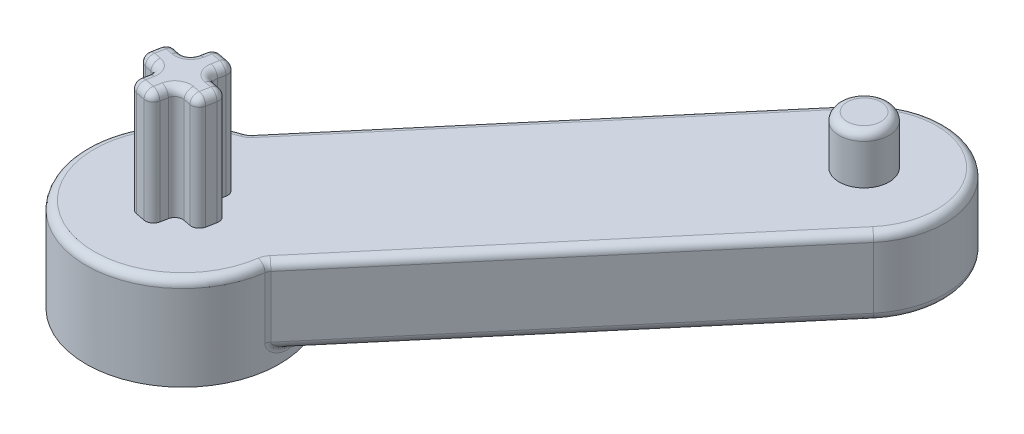
SolidWorks part; units mm, degrees
ref_plane "Front Plane" through (0, 0, 0) normal (0, 0, 1) x (1, 0, 0)
ref_plane "Top Plane" through (0, 0, 0) normal (0, 1, 0) x (1, 0, 0)
ref_plane "Right Plane" through (0, 0, 0) normal (1, 0, 0) x (0, 0, -1)
sketch "Sketch1" plane through (0, 0, 0) normal (0, 1, 0) x (1, 0, 0)
  line L1 (1.551, 4.203) -> (-1.551, 4.203) construction
  line L2 (1.551, 4.203) -> (1.551, 2.603) construction
  line L3 (1.551, 2.603) -> (-1.551, 2.603) construction
  line L4 (-1.551, 4.203) -> (-1.551, 2.603) construction
  line L5 (1.551, 4.203) -> (-1.551, 2.603) construction
  line L6 (1.551, 2.603) -> (-1.551, 4.203) construction
  line L7 (2.321, 4.7091) -> (2.321, 3.0089) construction
  line L8 (-2.321, 3.0089) -> (-2.321, 4.7091) construction
  line L10 (-2.321, 4.7091) -> (-2.321, 2.603) construction
  circle A0 centre (0, 0) radius 3.03 construction
  arc A1 (-1.551, 4.203) -> (1.551, 4.203) centre (0, 0) cw construction
  arc A2 (1.551, 2.603) -> (-1.551, 2.603) centre (0, 0) cw construction
  arc A3 (-2.321, 4.7091) -> (2.321, 4.7091) centre (0, 0) cw construction
  arc A4 (-2.321, 3.0089) -> (2.321, 3.0089) centre (0, 0) ccw
  arc A5 (2.321, 3.0089) -> (-1.9451, 3.2644) centre (0, 0) cw construction
  circle A6 centre (0, 0) radius 6
  circle A7 centre (0, 0) radius 5.25 construction
  arc A8 (-2.321, 3.0089) -> (2.321, 3.0089) centre (0, 0) cw
  point P3 (0, 3.403)
  dimension "D1" = 1.6
  dimension "D3" = 3.8
  dimension "D5" = 0.75
  dimension "D2" = 4.48
  dimension "D4" = 12
extrude "Boss-Extrude1" add sketch "Sketch1" along normal blind 5.3
sketch "Sketch2" plane through (0, 5.3, 0) normal (0, 1, 0) x (1, 0, 0)
  circle A0 centre (0, 0) radius 6
  dimension "D1" = 12
extrude "Boss-Extrude2" add sketch "Sketch2" along normal blind 0.5 and the other way offset from surface 3.5 other way up to face at (0, 0, 6)
sketch "Sketch3" plane through (0, 5.8, 0) normal (0, 1, 0) x (1, 0, 0)
  line L0 (-1.2146, -2.056) -> (-0.9379, -0.6327)
  line L1 (0.356, -2.3613) -> (-1.2146, -2.056)
  line L2 (0.356, -2.3613) -> (1.2146, 2.056) construction
  line L3 (1.2146, 2.056) -> (-0.356, 2.3613)
  line L4 (-1.2146, -2.056) -> (-0.356, 2.3613) construction
  line L5 (0.356, -2.3613) -> (-0.356, 2.3613) construction
  line L6 (1.2146, 2.056) -> (-1.2146, -2.056) construction
  line L7 (2.056, -1.2146) -> (-2.3613, -0.356) construction
  line L8 (2.056, -1.2146) -> (2.3613, 0.356)
  line L9 (2.3613, 0.356) -> (-2.056, 1.2146) construction
  line L10 (-2.3613, -0.356) -> (-2.056, 1.2146)
  line L11 (2.056, -1.2146) -> (-2.056, 1.2146) construction
  line L12 (2.3613, 0.356) -> (-2.3613, -0.356) construction
  line L13 (-0.9379, -0.6327) -> (-2.3613, -0.356)
  line L14 (-2.056, 1.2146) -> (-0.6327, 0.9379)
  line L15 (-0.6327, 0.9379) -> (-0.356, 2.3613)
  line L16 (1.2146, 2.056) -> (0.9379, 0.6327)
  line L17 (0.9379, 0.6327) -> (2.3613, 0.356)
  line L18 (2.056, -1.2146) -> (0.6327, -0.9379)
  line L19 (0.6327, -0.9379) -> (0.356, -2.3613)
  line L20 (-6, 0) -> (6, 0) construction
  line L21 (2.2087, -0.4293) -> (-2.2087, 0.4293) construction
  circle A0 centre (0, 0) radius 6 construction
  point P0 (0, 0)
  point P6 (0, 0)
  point P11 (0, 0)
  point P21 (0, 0)
  dimension "D1" = 4.5
  dimension "D2" = 1.6
  dimension "D3" = 11
extrude "Boss-Extrude3" add sketch "Sketch3" along normal blind 8
sketch "Sketch4" plane through (0, 3.5, 0) normal (0, -1, 0) x (1, 0, 0)
  circle A0 centre (0, 0) radius 6
  circle A1 centre (0, 0) radius 6
  circle A2 centre (0, 0) radius 6 construction
  circle A3 centre (0, 0) radius 6 construction
extrude "Boss-Extrude4" add sketch "Sketch4" against normal up to surface (2.3 mm away) contours A0 up to face at (0, 5.8, 0)
sketch "Sketch5" plane through (0, 13.8, 0) normal (0, 1, 0) x (1, 0, 0)
  circle A0 centre (0, 0) radius 2.388
extrude "Cut-Extrude1" cut sketch "Sketch5" against normal blind 1
sketch "Sketch6" plane through (0, 0, 0) normal (0, -1, 0) x (1, 0, 0)
  line L0 (0, 0) -> (10.7608, -12.7163) construction
  line L1 (15.5624, -26.1307) -> (23.196, -19.6709) construction
  line L2 (15.5624, -26.1307) -> (-1.6743, -5.7616)
  line L3 (-1.6743, -5.7616) -> (5.9593, 0.6981) construction
  line L4 (23.196, -19.6709) -> (5.9593, 0.6981)
  line L5 (15.5624, -26.1307) -> (5.9593, 0.6981) construction
  line L6 (-1.6743, -5.7616) -> (23.196, -19.6709) construction
  line L7 (3.8526, -4.5527) -> (19.3792, -22.9008) construction
  circle A0 centre (0, 0) radius 6 construction
  arc A2 (15.5624, -26.1307) -> (23.196, -19.6709) centre (19.3792, -22.9008) ccw
  arc A3 (24.3295, -15.6581) -> (17.8077, -12.9258) centre (22.4347, -11.031) ccw construction
  arc A4 (-1.6743, -5.7616) -> (5.9593, 0.6981) centre (0, 0) ccw
  point P0 (10.7608, -12.7163)
  dimension "D2" = 10
  dimension "D1" = 30
extrude "Boss-Extrude5" add sketch "Sketch6" against normal up to surface (5.8 mm away) up to face at (0, 5.8, 0)
sketch "Sketch7" plane through (0, 5.8, 0) normal (0, 1, 0) x (1, 0, 0)
  circle A0 centre (19.3792, 22.9008) radius 1.55
  dimension "D1" = 3.1
extrude "Boss-Extrude6" add sketch "Sketch7" along normal blind 3
sketch "Sketch8" plane through (0, 0, 0) normal (0, -1, 0) x (1, 0, 0)
  line L0 (-1.6743, -5.7616) -> (15.5624, -26.1307)
  line L1 (5.9593, 0.6981) -> (23.196, -19.6709)
  arc A0 (-1.6743, -5.7616) -> (5.9593, 0.6981) centre (0, 0) ccw
  arc A2 (23.196, -19.6709) -> (15.5624, -26.1307) centre (19.3792, -22.9008) cw
  arc A3 (5.9593, 0.6981) -> (-1.6743, -5.7616) centre (0, 0) ccw construction
extrude "Cut-Extrude2" cut sketch "Sketch8" against normal blind 1
fillet "Fillet1" radius 0.5 36 edges at (-0.9379, 9.3, 0.6327) (1.2146, 9.3, -2.056) (2.3613, 9.3, -0.356) (0.9379, 9.3, -0.6327) (-0.6327, 9.3, -0.9379) (-0.356, 9.3, -2.3613) (2.056, 9.3, 1.2146) (0.356, 9.3, 2.3613) (-2.056, 9.3, -1.2146) (-1.2146, 9.3, 2.056) (-2.3613, 9.3, 0.356) (0.6327, 9.3, 0.9379) (0.4293, 12.8, -2.2087) (1.0763, 12.8, -1.3443) (1.6496, 12.8, -0.4943) (2.2087, 12.8, 0.4293) (1.3443, 12.8, 1.0763) (0.4943, 12.8, 1.6496) (-0.4293, 12.8, 2.2087) (-1.0763, 12.8, 1.3443) (-1.6496, 12.8, 0.4943) (-2.2087, 12.8, -0.4293) (-1.3443, 12.8, -1.0763) (-0.4943, 12.8, -1.6496) (-3.8758, 5.8, 4.5802) (0, 0, 3.8) (14.5776, 5.8, -9.4864) (22.6091, 5.8, -26.7176) (19.3792, 8.8, -21.3508) (6.944, 5.8, -15.9462) (5.9593, 3.4, 0.6981) (-1.6743, 3.4, -5.7616) (14.5776, 1, -9.4864) (22.6091, 1, -26.7176) (6.944, 1, -15.9462) (3.8758, 1, -4.5802)
equation "\"Bearing Inner Diameter\"= 3.1mm"
equation "\"Bearing Outer Diameter\" = 7.25mm"
equation "\"ArmLength\" = 25mm"
equation "\"ArmLength2\" = 30mm"
equation "\"D1@Sketch6\"=\"ArmLength2\""
equation "\"D1@Sketch7\"=\"Bearing Inner Diameter\""
